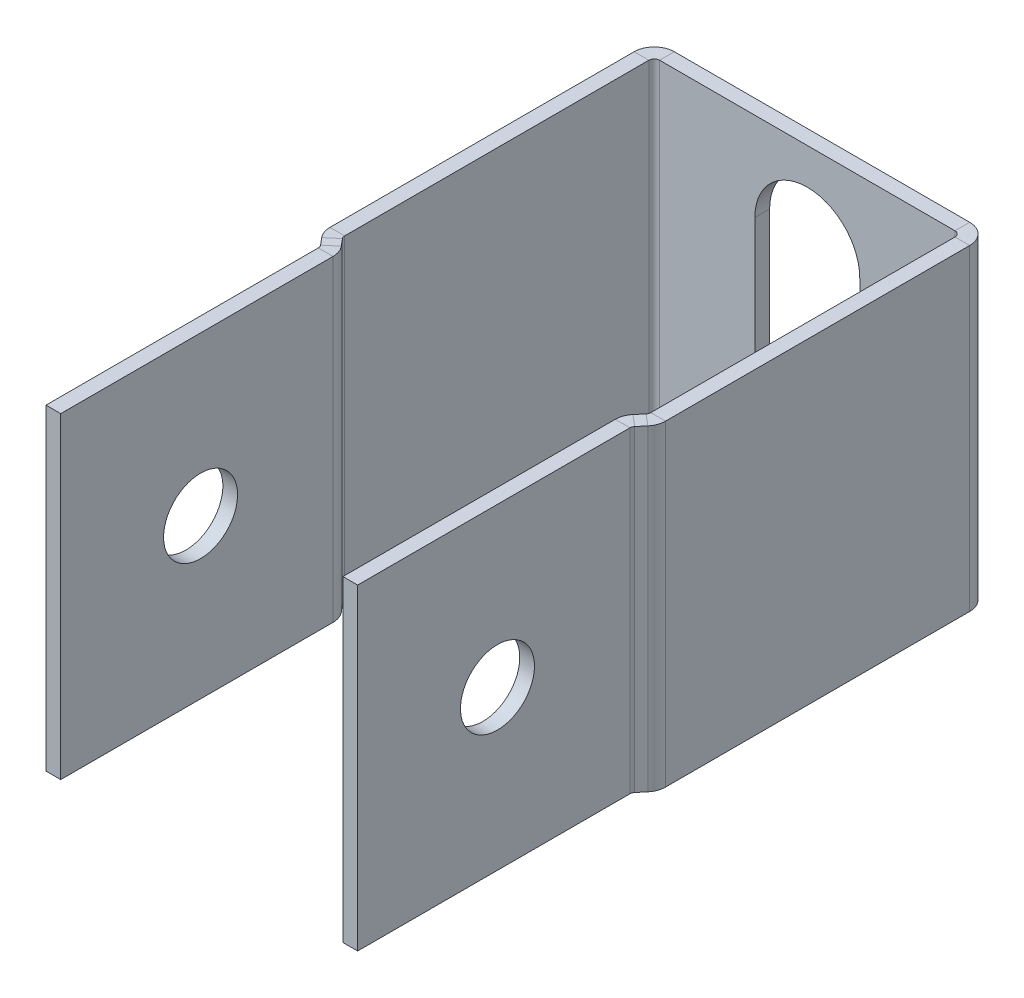
SolidWorks part; units mm, degrees
note: The reader was unsure of these and kept them because the rebuilt part matched: flange length of "Edge-Flange1", "Edge-Flange2", "Edge-Flange4".
material "1023 Carbon Steel Sheet (SS)"
ref_plane "Front Plane" through (0, 0, 0) normal (0, 0, 1) x (1, 0, 0)
ref_plane "Top Plane" through (0, 0, 0) normal (0, 1, 0) x (1, 0, 0)
ref_plane "Right Plane" through (0, 0, 0) normal (1, 0, 0) x (0, 0, -1)
sketch "Sketch1" plane through (0, 0, 0) normal (0, 0, 1) x (1, 0, 0)
  line L1 (-22.86, -21.59) -> (22.86, -21.59)
  line L2 (-22.86, -21.59) -> (-22.86, 21.59)
  line L3 (-22.86, 21.59) -> (22.86, 21.59)
  line L4 (22.86, -21.59) -> (22.86, 21.59)
  line L5 (-22.86, -21.59) -> (22.86, 21.59) construction
  line L6 (-22.86, 21.59) -> (22.86, -21.59) construction
  point P0 (0, 0)
  dimension "D1" = 45.72
  dimension "D2" = 43.18
base flange "Base-Flange1" sketch "Sketch1" thickness 2.0066 reverse thickness direction no parameters "D1"=0.7366
edge flange "Edge-Flange1" sketch "Sketch10" flange profiles "Sketch10", "Sketch11" flange angle 90 flange length 44.45 flange position material inside bend radius 0.7366 thickness 2.0066 relief rectangular parameters "D6"=10, "D8"=0.254
sketch "Sketch10" plane through (22.86, 0, 0) normal (1, 0, 0) x (0, 1, 0)
  line L2 (-21.59, 0) -> (-21.59, 42.4434)
  line L3 (-21.59, 42.4434) -> (21.59, 42.4434)
  line L4 (21.59, 42.4434) -> (21.59, 0)
  line L7 (-21.59, 0) -> (21.59, 0) construction
  line L8 (-21.59, 0) -> (21.59, 0)
sketch "Sketch11" plane through (-22.86, 0, 0) normal (-1, 0, 0) x (0, -1, 0)
  line L0 (-21.59, 0) -> (21.59, 0) construction
  line L1 (-21.59, 0) -> (21.59, 0)
  line L2 (-21.59, 0) -> (-21.59, 42.4434)
  line L3 (-21.59, 42.4434) -> (21.59, 42.4434)
  line L4 (21.59, 42.4434) -> (21.59, 0)
bend "EdgeBend1" bend radius 0.7366 bend angle 90 parameters "D5"=1
bend "EdgeBend2" bend radius 0.7366 bend angle 90 parameters "D5"=2
edge flange "Edge-Flange2" sketch "Sketch16" flange profiles "Sketch16", "Sketch17" flange angle 140 flange length 2.54 flange position material outside bend radius 0.7366 thickness 2.0066 relief rectangular parameters "D6"=10, "D8"=0.254
sketch "Sketch16" plane through (20.8534, 0, 42.4434) normal (0.766, 0, 0.6428) x (0, 1, 0)
  line L2 (-21.59, 0) -> (-21.59, 1.8097)
  line L3 (-21.59, 1.8097) -> (21.59, 1.8097)
  line L4 (21.59, 1.8097) -> (21.59, 0)
  line L35 (21.59, 0) -> (-21.59, 0) construction
  line L36 (21.59, 0) -> (-21.59, 0)
sketch "Sketch17" plane through (-20.8534, 0, 42.4434) normal (-0.766, 0, 0.6428) x (0, -1, 0)
  line L2 (-21.59, 0) -> (-21.59, 1.8097)
  line L3 (-21.59, 1.8097) -> (21.59, 1.8097)
  line L4 (21.59, 1.8097) -> (21.59, 0)
  line L15 (21.59, 0) -> (-21.59, 0) construction
  line L16 (21.59, 0) -> (-21.59, 0)
bend "EdgeBend3" bend radius 0.7366 bend angle 40 parameters "D5"=3
bend "EdgeBend4" bend radius 0.7366 bend angle 40 parameters "D5"=4
edge flange "Edge-Flange4" sketch "Sketch24" flange profiles "Sketch24", "Sketch25" flange angle 140 flange length 38.1 flange position material outside bend radius 0.7366 thickness 2.0066 relief rectangular parameters "D6"=10, "D8"=0.254
sketch "Sketch24" plane through (-21.2273, 0, 45.1195) normal (1, 0, 0) x (0, 1, 0)
  line L0 (-21.59, 0) -> (21.59, 0) construction
  line L1 (-21.59, 0) -> (21.59, 0)
  line L2 (-21.59, 0) -> (-21.59, 37.3697)
  line L3 (-21.59, 37.3697) -> (21.59, 37.3697)
  line L4 (21.59, 37.3697) -> (21.59, 0)
sketch "Sketch25" plane through (21.2273, 0, 45.1195) normal (-1, 0, 0) x (0, -1, 0)
  line L0 (-21.59, 0) -> (21.59, 0) construction
  line L1 (-21.59, 0) -> (21.59, 0)
  line L2 (-21.59, 0) -> (-21.59, 37.3697)
  line L3 (-21.59, 37.3697) -> (21.59, 37.3697)
  line L4 (21.59, 37.3697) -> (21.59, 0)
bend "EdgeBend6" bend radius 0.7366 bend angle 40 parameters "D5"=5
bend "EdgeBend7" bend radius 0.7366 bend angle 40 parameters "D5"=6
hole_wizard "3/8 Clearance Hole3" positions "Sketch34" profile "Sketch35" hole size "3/8" standard "ANSI Inch"
sketch "Sketch34" plane through (-21.2273, 0, 0) normal (-1, 0, 0) x (0, 0, 1)
  line L0 (82.4892, 21.59) -> (82.4892, -21.59) construction
  point P0 (63.4392, 0)
  dimension "D1" = 19.05
sketch "Sketch35" plane through (-21.2273, 0, 63.4392) normal (0, 1, 0) x (0, 0, 1)
  line L0 (0, 0) -> (0, 28.4295)
  line L1 (0, 28.4295) -> (5.0419, 25.4)
  line L2 (5.0419, 25.4) -> (5.0419, 0)
  line L5 (5.0419, 0) -> (0, 0)
  line L10 (0, 28.4295) -> (-5.0419, 25.4) construction
  line L11 (0, -6.35) -> (0, 107.95) construction
  dimension "Hole Dia." = 10.0838
  dimension "Hole Depth" = 25.4
  dimension "Drill Angle" = 118
hole_wizard "3/8 Clearance Hole4" positions "Sketch36" profile "Sketch37" hole size "3/8" standard "ANSI Inch"
sketch "Sketch36" plane through (21.2273, 0, 0) normal (1, 0, 0) x (0, 0, -1)
  line L0 (-82.4892, -21.59) -> (-82.4892, 21.59) construction
  point P0 (-63.4392, 0)
  dimension "D1" = 19.05
sketch "Sketch37" plane through (21.2273, 0, 63.4392) normal (0, 1, 0) x (0, 0, -1)
  line L0 (0, 0) -> (0, 28.4295)
  line L1 (0, 28.4295) -> (5.0419, 25.4)
  line L2 (5.0419, 25.4) -> (5.0419, 0)
  line L5 (5.0419, 0) -> (0, 0)
  line L10 (0, 28.4295) -> (-5.0419, 25.4) construction
  line L11 (0, -6.35) -> (0, 107.95) construction
  dimension "Hole Dia." = 10.0838
  dimension "Hole Depth" = 25.4
  dimension "Drill Angle" = 118
sketch "Sketch38" plane through (0, 0, -2.0066) normal (0, 0, -1) x (-1, 0, 0)
  line L0 (0, -9.525) -> (0, 9.525) construction
  line L1 (-7.1438, -9.525) -> (-7.1438, 9.525)
  line L2 (7.1438, -9.525) -> (7.1437, 9.525)
  arc A0 (-7.1438, -9.525) -> (7.1438, -9.525) centre (0, -9.525) ccw
  arc A1 (7.1437, 9.525) -> (-7.1438, 9.525) centre (0, 9.525) ccw
  point P2 (0, 0)
  dimension "D2" = 7.1437
  dimension "D1" = 19.05
extrude "Cut-Extrude1" cut sketch "Sketch38" against normal up to next normal cut yes
sketch "Bend-Lines1" [suppressed] plane through (0, 0, 0) normal (0, 1, 0) x (1, 0, 0)
sketch "Bounding-Box1" [suppressed] plane through (0, 0, 0) normal (0, 1, 0) x (1, 0, 0)
sheet metal parameters "Sheet-Metal1" thickness 2.0066 parameters "D1"=0.7366
flat pattern "Flat-Pattern1" [suppressed]
sketch "Bend-Lines2" plane through (0, 0, 0) normal (0, 1, 0) x (1, 0, 0)
sketch3d "Bounding-Box2" [suppressed]
  line L0 (20.955, -20.955, 0) -> (-20.955, -20.955, 0) construction
  line L1 (20.955, 20.955, 0) -> (-20.955, 20.955, 0) construction
  line L2 (20.955, -20.955, 0) -> (20.955, 20.955, 0) construction
  line L3 (-20.955, -20.955, 0) -> (-20.955, 20.955, 0) construction
sheet metal parameters "Sheet-Metal2" thickness 2.0066 parameters "D1"=0.7366
flat pattern "Flat-Pattern1"
sketch "Bend-Lines2" plane through (0, 0, 0) normal (0, 0, 1) x (1, 0, 0)
  line L0 (-19.5783, 20.955) -> (-19.5783, -20.955) construction
  line L1 (19.5783, -20.955) -> (19.5783, 20.955) construction
  line L2 (-19.5783, 20.955) -> (-19.5783, -20.955) construction
  line L3 (19.5783, -20.955) -> (19.5783, 20.955) construction
sketch3d "Bounding-Box2" [suppressed]
  line L0 (-62.6516, -20.955, 0) -> (62.6516, -20.955, 0) construction
  line L1 (-62.6516, 20.955, 0) -> (62.6516, 20.955, 0) construction
  line L2 (-62.6516, -20.955, 0) -> (-62.6516, 20.955, 0) construction
  line L3 (62.6516, -20.955, 0) -> (62.6516, 20.955, 0) construction
bend of the flat pattern "Flatten-<EdgeBend1>1"
bend of the flat pattern "Flatten-<EdgeBend2>1"
sheet metal parameters "Sheet-Metal3" thickness 2.0066 parameters "D1"=0.7366
flat pattern "Flat-Pattern1" [suppressed]
sketch "Bend-Lines2" plane through (0, 0, 0) normal (0, 0, 1) x (1, 0, 0)
  line L0 (-21.4833, 20.955) -> (-21.4833, -20.955) construction
  line L1 (21.4833, -20.955) -> (21.4833, 20.955) construction
  line L2 (-21.4833, 20.955) -> (-21.4833, -20.955) construction
  line L3 (21.4833, -20.955) -> (21.4833, 20.955) construction
  line L4 (-64.9348, 20.955) -> (-64.9348, -20.955) construction
  line L5 (64.9348, -20.955) -> (64.9348, 20.955) construction
  line L6 (-64.9348, 20.955) -> (-64.9348, -20.955) construction
  line L7 (64.9348, -20.955) -> (64.9348, 20.955) construction
sketch3d "Bounding-Box2" [suppressed]
  line L0 (-65.7518, -20.955, 0) -> (65.7518, -20.955, 0) construction
  line L1 (-65.7518, 20.955, 0) -> (65.7518, 20.955, 0) construction
  line L2 (-65.7518, -20.955, 0) -> (-65.7518, 20.955, 0) construction
  line L3 (65.7518, -20.955, 0) -> (65.7518, 20.955, 0) construction
bend of the flat pattern "Flatten-<EdgeBend1>1"
bend of the flat pattern "Flatten-<EdgeBend2>1"
bend of the flat pattern "Flatten-<EdgeBend3>1"
bend of the flat pattern "Flatten-<EdgeBend4>1"
sheet metal parameters "Sheet-Metal4" thickness 2.0066 parameters "D1"=0.7366
flat pattern "Flat-Pattern1"
sketch "Bend-Lines2" plane through (0, 0, 0) normal (0, 0, 1) x (1, 0, 0)
  line L0 (-21.4833, 19.05) -> (-21.4833, -19.05) construction
  line L1 (21.4833, -19.05) -> (21.4833, 19.05) construction
  line L2 (-21.4833, 19.05) -> (-21.4833, -19.05) construction
  line L3 (21.4833, -19.05) -> (21.4833, 19.05) construction
  line L4 (-64.8959, 19.05) -> (-64.8959, -19.05) construction
  line L5 (64.8959, -19.05) -> (64.8959, 19.05) construction
  line L6 (-64.8959, 19.05) -> (-64.8959, -19.05) construction
  line L7 (64.8959, -19.05) -> (64.8959, 19.05) construction
  line L8 (67.384, -19.05) -> (67.384, 19.05) construction
  line L9 (-67.384, 19.05) -> (-67.384, -19.05) construction
  line L10 (67.384, -19.05) -> (67.384, 19.05) construction
  line L11 (-67.384, 19.05) -> (-67.384, -19.05) construction
sketch3d "Bounding-Box2" [suppressed]
  line L0 (-105.0929, -19.05, 0) -> (105.0929, -19.05, 0) construction
  line L1 (-105.0929, 19.05, 0) -> (105.0929, 19.05, 0) construction
  line L2 (-105.0929, -19.05, 0) -> (-105.0929, 19.05, 0) construction
  line L3 (105.0929, -19.05, 0) -> (105.0929, 19.05, 0) construction
bend of the flat pattern "Flatten-<EdgeBend1>1"
bend of the flat pattern "Flatten-<EdgeBend2>1"
bend of the flat pattern "Flatten-<EdgeBend6>1"
bend of the flat pattern "Flatten-<EdgeBend7>1"
bend of the flat pattern "Flatten-<EdgeBend3>1"
bend of the flat pattern "Flatten-<EdgeBend4>1"
sheet metal parameters "Sheet-Metal8" thickness 2.0066 parameters "D1"=0.7366
flat pattern "Flat-Pattern1"
sketch "Bend-Lines2" plane through (0, 0, 0) normal (0, 0, 1) x (1, 0, 0)
  line L0 (-21.4833, 19.05) -> (-21.4833, -19.05) construction
  line L1 (21.4833, -19.05) -> (21.4833, 19.05) construction
  line L2 (-21.4833, 19.05) -> (-21.4833, -19.05) construction
  line L3 (21.4833, -19.05) -> (21.4833, 19.05) construction
  line L4 (-64.8959, 19.05) -> (-64.8959, -19.05) construction
  line L5 (64.8959, -19.05) -> (64.8959, 19.05) construction
  line L6 (-64.8959, 19.05) -> (-64.8959, -19.05) construction
  line L7 (64.8959, -19.05) -> (64.8959, 19.05) construction
  line L8 (67.384, -19.05) -> (67.384, 19.05) construction
  line L9 (-67.384, 19.05) -> (-67.384, -19.05) construction
  line L10 (67.384, -19.05) -> (67.384, 19.05) construction
  line L11 (-67.384, 19.05) -> (-67.384, -19.05) construction
sketch3d "Bounding-Box2" [suppressed]
  line L0 (-105.0929, -19.05, 0) -> (105.0929, -19.05, 0) construction
  line L1 (-105.0929, 19.05, 0) -> (105.0929, 19.05, 0) construction
  line L2 (-105.0929, -19.05, 0) -> (-105.0929, 19.05, 0) construction
  line L3 (105.0929, -19.05, 0) -> (105.0929, 19.05, 0) construction
bend of the flat pattern "Flatten-<EdgeBend1>1"
bend of the flat pattern "Flatten-<EdgeBend2>1"
bend of the flat pattern "Flatten-<EdgeBend6>1"
bend of the flat pattern "Flatten-<EdgeBend7>1"
bend of the flat pattern "Flatten-<EdgeBend3>1"
bend of the flat pattern "Flatten-<EdgeBend4>1"
sheet metal parameters "Sheet-Metal9" thickness 2.0066 parameters "D1"=0.7366
flat pattern "Flat-Pattern1"
sketch "Bend-Lines2" plane through (0, 0, 0) normal (0, 0, 1) x (1, 0, 0)
  line L0 (-21.4833, 21.59) -> (-21.4833, -21.59) construction
  line L1 (21.4833, -21.59) -> (21.4833, 21.59) construction
  line L2 (-21.4833, 21.59) -> (-21.4833, -21.59) construction
  line L3 (21.4833, -21.59) -> (21.4833, 21.59) construction
  line L4 (-64.8959, 21.59) -> (-64.8959, -21.59) construction
  line L5 (64.8959, -21.59) -> (64.8959, 21.59) construction
  line L6 (-64.8959, 21.59) -> (-64.8959, -21.59) construction
  line L7 (64.8959, -21.59) -> (64.8959, 21.59) construction
  line L8 (67.384, -21.59) -> (67.384, 21.59) construction
  line L9 (-67.384, 21.59) -> (-67.384, -21.59) construction
  line L10 (67.384, -21.59) -> (67.384, 21.59) construction
  line L11 (-67.384, 21.59) -> (-67.384, -21.59) construction
sketch3d "Bounding-Box2" [suppressed]
  line L0 (-105.0929, -21.59, 0) -> (105.0929, -21.59, 0) construction
  line L1 (-105.0929, 21.59, 0) -> (105.0929, 21.59, 0) construction
  line L2 (-105.0929, -21.59, 0) -> (-105.0929, 21.59, 0) construction
  line L3 (105.0929, -21.59, 0) -> (105.0929, 21.59, 0) construction
bend of the flat pattern "Flatten-<EdgeBend1>1"
bend of the flat pattern "Flatten-<EdgeBend2>1"
bend of the flat pattern "Flatten-<EdgeBend6>1"
bend of the flat pattern "Flatten-<EdgeBend7>1"
bend of the flat pattern "Flatten-<EdgeBend3>1"
bend of the flat pattern "Flatten-<EdgeBend4>1"
sheet metal parameters "Sheet-Metal10" thickness 2.0066 parameters "D1"=0.7366
flat pattern "Flat-Pattern1"
sketch "Bend-Lines2" plane through (0, 0, 0) normal (0, 0, 1) x (1, 0, 0)
  line L0 (-21.4833, 21.59) -> (-21.4833, -21.59) construction
  line L1 (21.4833, -21.59) -> (21.4833, 21.59) construction
  line L2 (-21.4833, 21.59) -> (-21.4833, -21.59) construction
  line L3 (21.4833, -21.59) -> (21.4833, 21.59) construction
  line L4 (-64.8959, 21.59) -> (-64.8959, -21.59) construction
  line L5 (64.8959, -21.59) -> (64.8959, 21.59) construction
  line L6 (-64.8959, 21.59) -> (-64.8959, -21.59) construction
  line L7 (64.8959, -21.59) -> (64.8959, 21.59) construction
  line L8 (67.384, -21.59) -> (67.384, 21.59) construction
  line L9 (-67.384, 21.59) -> (-67.384, -21.59) construction
  line L10 (67.384, -21.59) -> (67.384, 21.59) construction
  line L11 (-67.384, 21.59) -> (-67.384, -21.59) construction
sketch3d "Bounding-Box2" [suppressed]
  line L0 (-105.0929, -21.59, 0) -> (105.0929, -21.59, 0) construction
  line L1 (-105.0929, 21.59, 0) -> (105.0929, 21.59, 0) construction
  line L2 (-105.0929, -21.59, 0) -> (-105.0929, 21.59, 0) construction
  line L3 (105.0929, -21.59, 0) -> (105.0929, 21.59, 0) construction
bend of the flat pattern "Flatten-<EdgeBend1>1"
bend of the flat pattern "Flatten-<EdgeBend2>1"
bend of the flat pattern "Flatten-<EdgeBend6>1"
bend of the flat pattern "Flatten-<EdgeBend7>1"
bend of the flat pattern "Flatten-<EdgeBend3>1"
bend of the flat pattern "Flatten-<EdgeBend4>1"
